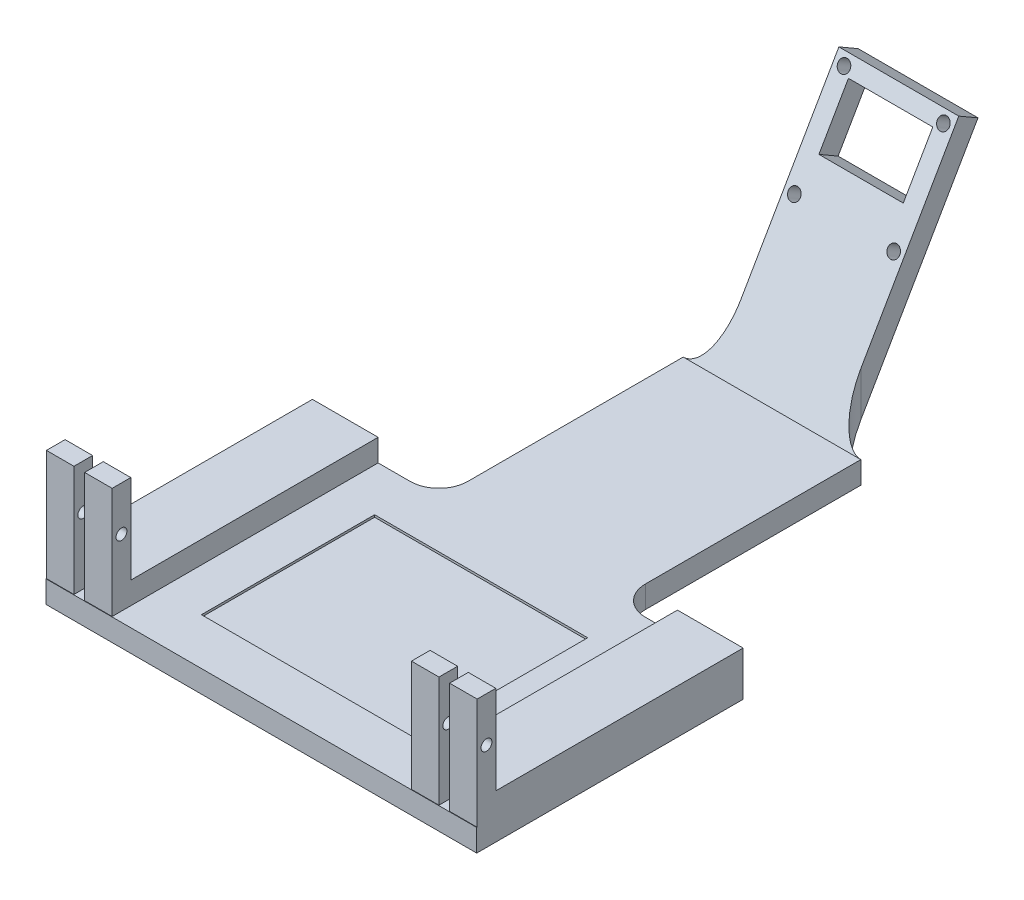
SolidWorks part; units mm, degrees
ref_plane "Front Plane" through (0, 0, 0) normal (0, 0, 1) x (1, 0, 0)
ref_plane "Top Plane" through (0, 0, 0) normal (0, 1, 0) x (1, 0, 0)
ref_plane "Right Plane" through (0, 0, 0) normal (1, 0, 0) x (0, 0, -1)
sketch "Sketch1" plane through (0, 0, 0) normal (0, 1, 0) x (1, 0, 0)
  line L0 (-25.4, 38.1) -> (-61.595, 38.1)
  line L1 (61.595, -38.1) -> (-61.595, -38.1)
  line L2 (61.595, -38.1) -> (61.595, 38.1)
  line L3 (61.595, 38.1) -> (25.4, 38.1)
  line L4 (-61.595, -38.1) -> (-61.595, 38.1)
  line L5 (61.595, -38.1) -> (-61.595, 38.1) construction
  line L6 (61.595, 38.1) -> (-61.595, -38.1) construction
  line L8 (-25.4, 38.1) -> (-25.4, 107.95)
  line L9 (-25.4, 107.95) -> (25.4, 107.95)
  line L10 (25.4, 38.1) -> (25.4, 107.95)
  point P0 (0, 0)
  point P10 (0, 107.95)
  dimension "D1" = 123.19
  dimension "D2" = 76.2
  dimension "D3" = 69.85
  dimension "D4" = 50.8
extrude "Boss-Extrude1" add sketch "Sketch1" along normal blind 6.35
sketch "Sketch2" plane through (0, 6.35, 0) normal (0, 1, 0) x (1, 0, 0)
  line L1 (30.48, -24.765) -> (-30.48, -24.765)
  line L2 (30.48, -24.765) -> (30.48, 24.765)
  line L3 (30.48, 24.765) -> (-30.48, 24.765)
  line L4 (-30.48, -24.765) -> (-30.48, 24.765)
  line L5 (30.48, -24.765) -> (-30.48, 24.765) construction
  line L6 (30.48, 24.765) -> (-30.48, -24.765) construction
  point P0 (0, 0)
  dimension "D1" = 60.96
  dimension "D2" = 49.53
extrude "Cut-Extrude1" cut sketch "Sketch2" against normal blind 0.635
sketch "Sketch5" plane through (0, 6.35, 0) normal (0, 1, 0) x (1, 0, 0)
  line L0 (-61.595, 38.1) -> (-61.595, -38.1) construction
  line L1 (-42.799, -37.9794) -> (-61.595, -37.9794)
  line L2 (-42.799, -37.9794) -> (-42.799, -32.6454)
  line L3 (-42.799, -32.6454) -> (-61.595, -32.6454)
  line L4 (-61.595, -37.9794) -> (-61.595, -32.6454)
  line L5 (-53.721, -32.6454) -> (-50.673, -32.6454)
  line L6 (-53.721, -32.6454) -> (-53.721, -37.9794)
  line L7 (-53.721, -37.9794) -> (-50.673, -37.9794)
  line L8 (-50.673, -32.6454) -> (-50.673, -37.9794)
  point P9 (-52.197, -37.9794)
  point P10 (-52.197, -37.9794)
  line M9 (-61.595, 38.1) -> (-61.595, -38.1)
  dimension "D1" = 18.796
  dimension "D2" = 3.048
  dimension "D3" = 5.334
extrude "Boss-Extrude2" add sketch "Sketch5" along normal blind 31.75 separate body contours L3 L8 L1 M9 | L6 L3 L4 L1 region at (-46.736, 6.35, 35.3124) region at (-57.658, 6.35, 35.3124)
mirror "Mirror4" about plane through (0, 0, 0) normal (1, 0, 0) of "Boss-Extrude2"
sketch "Sketch7" plane through (61.595, 0, 0) normal (1, 0, 0) x (0, 0, -1)
  line L0 (-32.6454, 38.1) -> (-37.9794, 38.1) construction
  line L1 (-32.6454, 6.35) -> (38.1, 6.35) construction
  circle A0 centre (-35.3124, 25.4) radius 1.5558
  point P2 (0, 0)
  point P5 (0, 0)
  point P6 (-35.3124, 38.1)
  dimension "D1" = 3.1115
  dimension "D2" = 19.05
extrude "Cut-Extrude2" cut sketch "Sketch7" against normal through all
sketch "Sketch8" plane through (25.4, 0, 0) normal (1, 0, 0) x (0, 0, -1)
  line L0 (111.6162, 0) -> (149.7162, 65.9911)
  line L1 (38.1, 0) -> (107.95, 0) construction
  line L2 (149.7162, 65.9911) -> (144.2169, 69.1661)
  line L3 (144.2169, 69.1661) -> (107.95, 6.35)
  line L4 (111.6162, 0) -> (107.95, 0)
  line L6 (102.3658, 0) -> (139.7334, 0) construction
  line L7 (107.95, 6.35) -> (107.95, 0)
  dimension "D1" = 6.35
  dimension "D2" = 60
  dimension "D3" = 76.2
extrude "Boss-Extrude3" add sketch "Sketch8" against normal blind 34.29 from offset 8.255 offset against normal yes
sketch "Sketch9" plane through (0, -45.1562, -78.2129) normal (0, 0.5, 0.866) x (1, 0, 0)
  line L0 (-17.145, 132.0081) -> (17.145, 132.0081) construction
  line L1 (-17.145, 132.0081) -> (-17.145, 59.4743) construction
  line L2 (0, 126.0032) -> (0, 101.7574) construction
  line L3 (-23.7035, 114.8631) -> (28.5526, 114.8631) construction
  line L5 (-12.065, 110.4233) -> (12.065, 110.4233)
  line L6 (-12.065, 110.4233) -> (-12.065, 127.3143)
  line L7 (-12.065, 127.3143) -> (12.065, 127.3143)
  line L8 (12.065, 110.4233) -> (12.065, 127.3143)
  circle A0 centre (-14.2113, 129.0744) radius 1.7399
  circle A1 centre (14.2113, 129.0744) radius 1.7399
  circle A2 centre (14.2113, 100.6518) radius 1.7399
  circle A3 centre (-14.2113, 100.6518) radius 1.7399
  point P21 (0, 110.4233)
  point P22 (0, 0)
  dimension "D3" = 3.4798
  dimension "D1" = 2.9337
  dimension "D2" = 2.9337
  dimension "D4" = 17.145
  dimension "D5" = 24.13
  dimension "D6" = 16.891
  dimension "D7" = 4.6938
extrude "Cut-Extrude3" cut sketch "Sketch9" against normal through all
sketch "Sketch11" plane through (0, 6.35, 0) normal (0, 1, 0) x (1, 0, 0)
  line L0 (-25.4, 38.1) -> (-61.595, 38.1) construction
  line L1 (-61.595, -32.6454) -> (-42.799, -32.6454)
  line L2 (-61.595, -32.6454) -> (-61.595, 38.1)
  line L3 (-61.595, 38.1) -> (-42.799, 38.1)
  line L4 (-42.799, -32.6454) -> (-42.799, 38.1)
  line L5 (-42.799, -37.9794) -> (-42.799, -32.6454) construction
  line L7 (42.799, -32.6454) -> (61.595, -32.6454)
  line L8 (42.799, -32.6454) -> (42.799, 38.1)
  line L9 (42.799, 38.1) -> (61.595, 38.1)
  line L10 (61.595, -32.6454) -> (61.595, 38.1)
extrude "Boss-Extrude6" add sketch "Sketch11" along normal blind 6.35
fillet "Fillet1" radius 8.255 4 edges at (-17.145, 3.175, -107.95) (17.145, 3.175, -107.95) (-25.4, 3.175, -38.1) (25.4, 3.175, -38.1)
